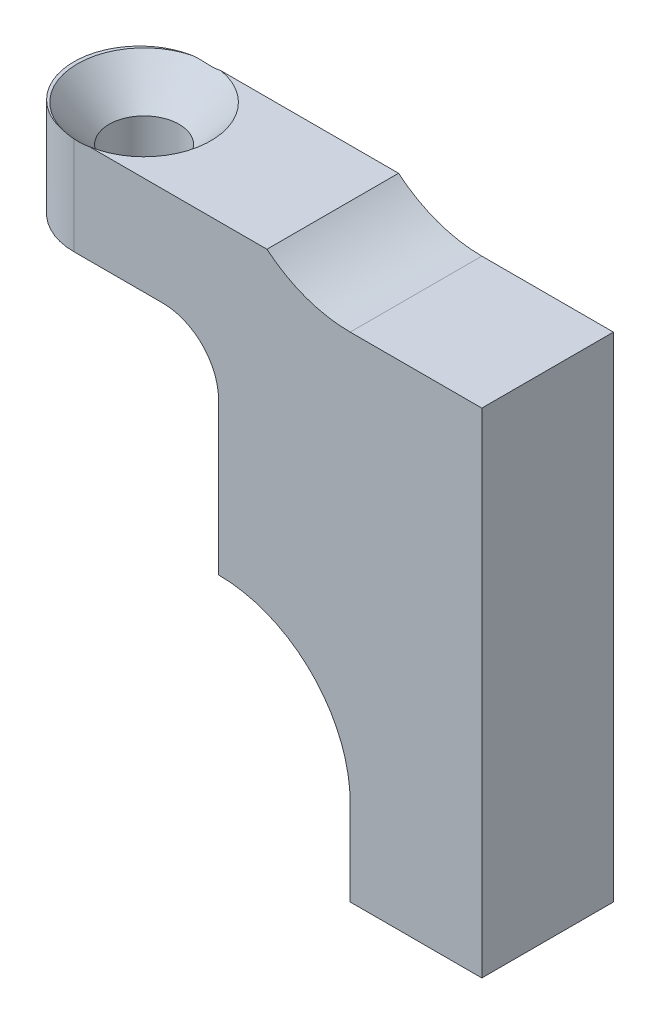
SolidWorks part; units mm, degrees
material "Plain Carbon Steel"
ref_plane "Front Plane" through (0, 0, 0) normal (0, 0, 1) x (1, 0, 0)
ref_plane "Top Plane" through (0, 0, 0) normal (0, 1, 0) x (1, 0, 0)
ref_plane "Right Plane" through (0, 0, 0) normal (1, 0, 0) x (0, 0, -1)
sketch "Sketch1" plane through (0, 0, 0) normal (0, 0, 1) x (1, 0, 0)
  line L0 (0, 0) -> (0, 47.625)
  line L1 (0, 47.625) -> (-12.7, 47.625)
  line L2 (-20.7346, 50.5333) -> (-45.72, 50.5333)
  line L3 (-45.72, 50.5333) -> (-45.72, 41.0083)
  line L4 (-45.72, 41.0083) -> (-30.7954, 41.0083)
  line L5 (0, 0) -> (-12.7, 0)
  line L6 (-25.4, 20.9797) -> (-25.4, 35.6129)
  line L7 (-12.7, 0) -> (-12.7, 8.2797)
  arc A0 (-12.7, 47.625) -> (-20.7346, 50.5333) centre (-12.7, 60.1775) cw
  arc A4 (-25.4, 35.6129) -> (-30.7954, 41.0083) centre (-30.7954, 35.6129) ccw
  arc A5 (-12.7, 8.2797) -> (-25.4, 20.9797) centre (-25.4, 8.2797) ccw
  dimension "D1" = 9.525
  dimension "D4" = 45.72
  dimension "D2" = 12.7
  dimension "D3" = 41.0083
  dimension "D5" = 47.625
  dimension "D6" = 25.4
extrude "Boss-Extrude1" add sketch "Sketch1" along normal blind 12.7
sketch "Sketch2" plane through (0, 50.5333, 0) normal (0, 1, 0) x (1, 0, 0)
  line L0 (0, -12.7) -> (0, 0) construction
  point P0 (-38.9382, -6.35)
  dimension "D1" = 38.9382
hole_wizard "CSK for 1/4 Flat Head Machine Screw1" positions "Sketch2" profile "Sketch3" countersink size "1/4" standard "ANSI Inch" end condition through all
sketch "Sketch3" plane through (-38.9382, 50.5333, 6.35) normal (1, 0, 0) x (0, 0, 1)
  line L0 (0, 0) -> (0, 50.5333)
  line L1 (0, 50.5333) -> (3.3782, 50.5333)
  line L2 (3.3782, 50.5333) -> (3.3782, 3.5209)
  line L3 (3.3782, 3.5209) -> (6.4389, 0)
  line L5 (6.4389, 0) -> (0, 0)
  line L6 (-3.3782, 3.5209) -> (-6.4389, 0) construction
  line L11 (0, -6.35) -> (0, 107.95) construction
  dimension "Thru Hole Dia." = 6.7564
  dimension "Thru Hole Depth" = 50.5333
  dimension "Near C'Sink Dia." = 12.8778
  dimension "Near C'Sink Angle" = 82
fillet "Fillet1" 2 edges at (-45.72, 45.7708, 12.7) (-45.72, 45.7708, 0) type full round first side face at (-23.64, 34.4088, 12.7) second side face at (-23.64, 34.4088, 0) middle face at (-45.72, 45.7708, 6.35)
